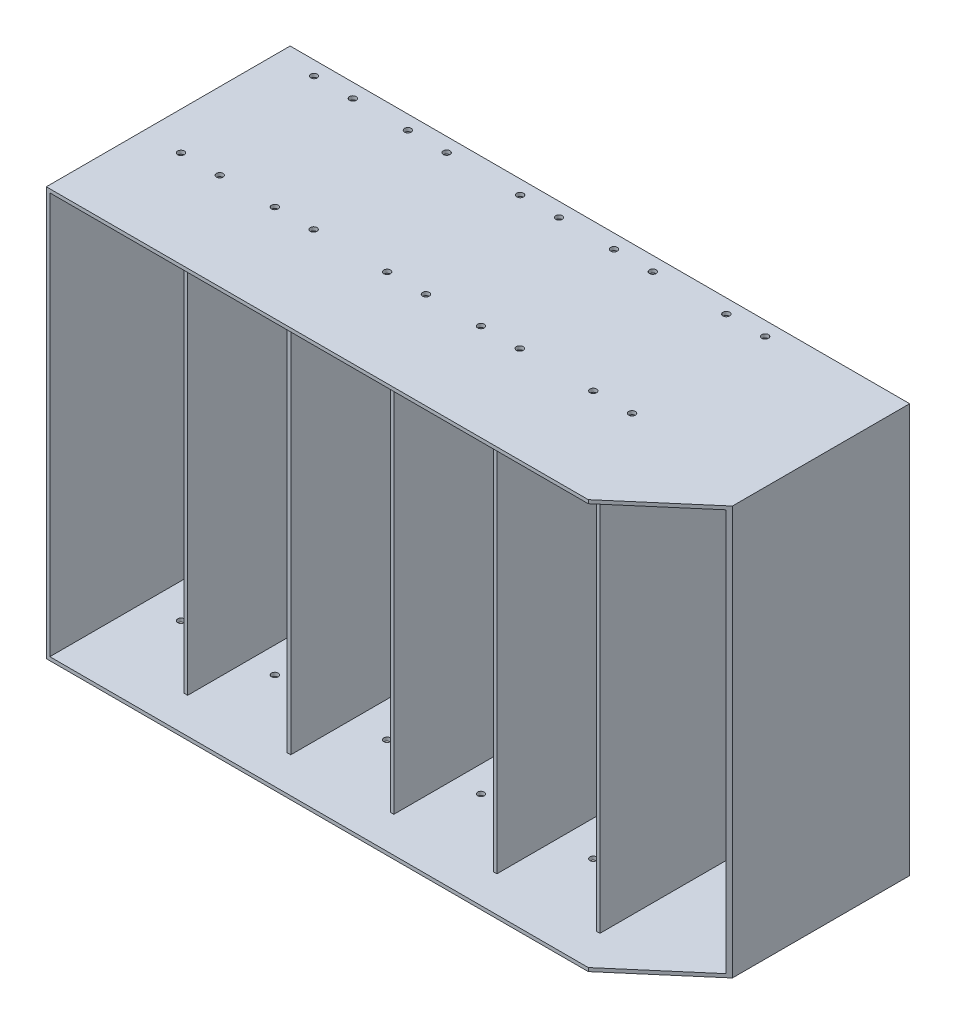
SolidWorks part; units mm, degrees
material "Custom Plastic"
ref_plane "X-Y Datum" through (0, 0, 0) normal (0, 0, 1) x (1, 0, 0)
ref_plane "X-Z Datum" through (0, 0, 0) normal (0, 1, 0) x (1, 0, 0)
ref_plane "Y-Z Datum" through (0, 0, 0) normal (1, 0, 0) x (0, 0, -1)
sketch "Sketch1" plane through (0, 0, 0) normal (0, 0, 1) x (1, 0, 0)
  line L0 (-276.225, 0) -> (276.225, 0) construction
  line L1 (-276.225, 181.1563) -> (276.225, 181.1563)
  line L2 (-276.225, 181.1563) -> (-276.225, -181.1563)
  line L3 (-276.225, -181.1563) -> (276.225, -181.1563)
  line L4 (276.225, 181.1563) -> (276.225, -181.1563)
  line L5 (-276.225, 181.1563) -> (276.225, -181.1563) construction
  line L6 (-276.225, -181.1563) -> (276.225, 181.1563) construction
  line L7 (-273.8438, 178.775) -> (-190.2437, 178.775) construction
  line L8 (-273.8438, 178.775) -> (-273.8438, -178.775) construction
  line L9 (-273.8438, -178.775) -> (-190.2437, -178.775) construction
  line L10 (-190.2437, 178.775) -> (-190.2437, -178.775) construction
  line L11 (-273.8438, 178.775) -> (-190.2437, -178.775) construction
  line L12 (-273.8438, -178.775) -> (-190.2437, 178.775) construction
  line L13 (-187.0687, -181.1563) -> (-187.0687, 181.1563)
  line L14 (-279.4, 184.3313) -> (279.4, 184.3313)
  line L15 (279.4, 184.3313) -> (279.4, -184.3313)
  line L16 (-279.4, -184.3313) -> (279.4, -184.3313)
  line L17 (-279.4, 184.3313) -> (-279.4, -184.3313)
  line L18 (-183.8937, -181.1563) -> (-183.8937, 181.1563)
  line L19 (-187.0687, 0) -> (-183.8937, 0) construction
  line L20 (-180.8797, 178.775) -> (-180.8797, -178.775) construction
  line L21 (-180.8797, 178.775) -> (-97.2797, 178.775) construction
  line L22 (-97.2797, 178.775) -> (-97.2797, -178.775) construction
  line L23 (-180.8797, -178.775) -> (-97.2797, -178.775) construction
  line L24 (-94.1047, -181.1563) -> (-94.1047, 181.1563)
  line L25 (-90.9297, -181.1563) -> (-90.9297, 181.1563)
  line L26 (-87.9157, 178.775) -> (-87.9157, -178.775) construction
  line L27 (-87.9157, 178.775) -> (-4.3157, 178.775) construction
  line L28 (-4.3157, 178.775) -> (-4.3157, -178.775) construction
  line L29 (-87.9157, -178.775) -> (-4.3157, -178.775) construction
  line L30 (-1.1407, -181.1563) -> (-1.1407, 181.1563)
  line L31 (2.0343, -181.1563) -> (2.0343, 181.1563)
  line L32 (5.0483, 178.775) -> (5.0483, -178.775) construction
  line L33 (5.0483, 178.775) -> (88.6483, 178.775) construction
  line L34 (88.6483, 178.775) -> (88.6483, -178.775) construction
  line L35 (5.0483, -178.775) -> (88.6483, -178.775) construction
  line L36 (91.8233, -181.1563) -> (91.8233, 181.1563)
  line L37 (94.9983, -181.1563) -> (94.9983, 181.1563)
  line L38 (98.0123, 178.775) -> (98.0123, -178.775) construction
  line L39 (98.0123, 178.775) -> (181.6123, 178.775) construction
  line L40 (181.6123, 178.775) -> (181.6123, -178.775) construction
  line L41 (98.0123, -178.775) -> (181.6123, -178.775) construction
  line L42 (184.7873, -181.1563) -> (184.7873, 181.1563)
  line L43 (187.9623, -181.1563) -> (187.9623, 181.1563)
  line L44 (-180.8797, -178.775) -> (-97.2797, 178.775) construction
  line L45 (-180.8797, 178.775) -> (-97.2797, -178.775) construction
  line L46 (-87.9157, -178.775) -> (-4.3157, 178.775) construction
  line L47 (-87.9157, 178.775) -> (-4.3157, -178.775) construction
  line L48 (5.0483, -178.775) -> (88.6483, 178.775) construction
  line L49 (5.0483, 178.775) -> (88.6483, -178.775) construction
  line L50 (98.0123, -178.775) -> (181.6123, 178.775) construction
  line L51 (98.0123, 178.775) -> (181.6123, -178.775) construction
  point P0 (0, 0)
  point P6 (-232.0437, 0)
  point P23 (-185.4812, 0)
  point P24 (-139.0797, 0)
  dimension "D1" = 357.55
  dimension "D2" = 83.6
  dimension "D3" = 2.3813
  dimension "D4" = 2.3813
  dimension "D5" = 3.175
  dimension "D8" = 46.5625
  dimension "D10" = 558.8
  dimension "D12" = 92.964
  dimension "D6" = 3.175
  dimension "D7" = 3.175
  dimension "D9" = 5
  dimension "D11" = 5
extrude "Boss-Extrude1" add sketch "Sketch1" along normal blind 3.175 contours L3 L13 L1 L2 | L3 L24 L1 L18 | L3 L18 L1 L13 | L14 L17 L16 L15 L1 L4 L3 L2 | L3 L30 L1 L25 | L3 L25 L1 L24 | L3 L36 L1 L31 | L3 L31 L1 L30 | L3 L42 L1 L37 | L3 L37 L1 L36 | L43 L3 L4 L1 | L3 L43 L1 L42 region at (-231.6469, 0, 0) region at (-185.4812, 0, 0) region at (-138.9992, 0, 0) region at (-92.5172, 0, 0) region at (-46.0352, 0, 0) region at (0.4468, 0, 0) region at (46.9288, 0, 0) region at (93.4108, 0, 0) region at (139.8928, 0, 0) region at (186.3748, 0, 0) region at (232.0936, 0, 0) region at (0, 183.6618, 0)
sketch "Sketch2" plane through (0, 0, 3.175) normal (0, 0, 1) x (1, 0, 0)
  line L0 (-187.0687, -181.1563) -> (-187.0687, 181.1563) construction
  line L1 (-94.1047, -181.1563) -> (-94.1047, 181.1563) construction
  line L2 (-183.8937, -181.1563) -> (-183.8937, 181.1563) construction
  line L3 (91.8233, -181.1563) -> (91.8233, 181.1563) construction
  line L4 (276.225, 181.1563) -> (-276.225, 181.1563)
  line L5 (276.225, -181.1563) -> (276.225, 181.1563)
  line L6 (-276.225, -181.1563) -> (276.225, -181.1563)
  line L7 (-276.225, 181.1563) -> (-276.225, -181.1563)
  line L8 (276.225, 181.1563) -> (-276.225, 181.1563)
  line L9 (276.225, -181.1563) -> (276.225, 181.1563)
  line L10 (-276.225, -181.1563) -> (276.225, -181.1563)
  line L11 (-276.225, 181.1563) -> (-276.225, -181.1563)
  line L12 (-279.4, -184.3313) -> (279.4, -184.3313)
  line L13 (-279.4, 184.3313) -> (-279.4, -184.3313)
  line L14 (279.4, 184.3313) -> (-279.4, 184.3313)
  line L15 (279.4, -184.3313) -> (279.4, 184.3313)
  line L16 (-279.4, -184.3313) -> (279.4, -184.3313)
  line L17 (-279.4, 184.3313) -> (-279.4, -184.3313)
  line L18 (279.4, 184.3313) -> (-279.4, 184.3313)
  line L19 (279.4, -184.3313) -> (279.4, 184.3313)
  line L20 (2.0343, -181.1563) -> (2.0343, 181.1563) construction
  line L21 (-1.1407, -181.1563) -> (-1.1407, 181.1563) construction
  line L22 (-90.9297, -181.1563) -> (-90.9297, 181.1563) construction
  line L23 (187.9623, -181.1563) -> (187.9623, 181.1563) construction
  line L24 (184.7873, -181.1563) -> (184.7873, 181.1563) construction
  line L25 (94.9983, -181.1563) -> (94.9983, 181.1563) construction
  line L26 (-187.0687, -181.1563) -> (-187.0687, 181.1563)
  line L27 (-94.1047, -181.1563) -> (-94.1047, 181.1563)
  line L28 (-183.8937, -181.1563) -> (-183.8937, 181.1563)
  line L29 (91.8233, -181.1563) -> (91.8233, 181.1563)
  line L30 (2.0343, -181.1563) -> (2.0343, 181.1563)
  line L31 (-1.1407, -181.1563) -> (-1.1407, 181.1563)
  line L32 (-90.9297, -181.1563) -> (-90.9297, 181.1563)
  line L33 (187.9623, -181.1563) -> (187.9623, 181.1563)
  line L34 (184.7873, -181.1563) -> (184.7873, 181.1563)
  line L35 (94.9983, -181.1563) -> (94.9983, 181.1563)
  line M9 (279.4, 184.3313) -> (-279.4, 184.3313)
  line M10 (-279.4, 184.3313) -> (-279.4, -184.3313)
  line M11 (-279.4, -184.3313) -> (279.4, -184.3313)
  line M12 (279.4, -184.3313) -> (279.4, 184.3313)
  dimension "D1" = 0
  dimension "D2" = 0
extrude "Boss-Extrude2" add sketch "Sketch2" along normal blind 184.725 contours L11 L8 L9 L10 M12 M9 M10 M11 | L10 L28 L8 L26 | L10 L32 L8 L27 | L31 L10 L30 L8 | L10 L35 L8 L29 | L34 L10 L33 L8 region at (186.3748, 0, 3.175) region at (93.4108, 0, 3.175) region at (0.4468, 0, 3.175) region at (-92.5172, 0, 3.175) region at (-185.4812, 0, 3.175) region at (-278.7305, 0, 3.175)
sketch "Sketch3" plane through (0, 0, 187.9) normal (0, 0, 1) x (1, 0, 0)
  line L0 (-187.0687, -181.1563) -> (-187.0687, 181.1563) construction
  line L1 (-94.1047, -181.1563) -> (-94.1047, 181.1563) construction
  line L2 (-183.8937, -181.1563) -> (-183.8937, 181.1563) construction
  line L3 (91.8233, -181.1563) -> (91.8233, 181.1563) construction
  line L4 (276.225, 181.1563) -> (-276.225, 181.1563)
  line L5 (276.225, -181.1563) -> (276.225, 181.1563)
  line L6 (-276.225, -181.1563) -> (276.225, -181.1563)
  line L7 (-276.225, 181.1563) -> (-276.225, -181.1563)
  line L8 (276.225, 181.1563) -> (-276.225, 181.1563)
  line L9 (276.225, -181.1563) -> (276.225, 181.1563)
  line L10 (-276.225, -181.1563) -> (276.225, -181.1563)
  line L11 (-276.225, 181.1563) -> (-276.225, -181.1563)
  line L12 (-279.4, -184.3313) -> (279.4, -184.3313)
  line L13 (-279.4, 184.3313) -> (-279.4, -184.3313)
  line L14 (279.4, 184.3313) -> (-279.4, 184.3313)
  line L15 (279.4, -184.3313) -> (279.4, 184.3313)
  line L16 (-279.4, -184.3313) -> (279.4, -184.3313)
  line L17 (-279.4, 184.3313) -> (-279.4, -184.3313)
  line L18 (279.4, 184.3313) -> (-279.4, 184.3313)
  line L19 (279.4, -184.3313) -> (279.4, 184.3313)
  line L20 (2.0343, -181.1563) -> (2.0343, 181.1563) construction
  line L21 (-1.1407, -181.1563) -> (-1.1407, 181.1563) construction
  line L22 (-90.9297, -181.1563) -> (-90.9297, 181.1563) construction
  line L23 (187.9623, -181.1563) -> (187.9623, 181.1563) construction
  line L24 (184.7873, -181.1563) -> (184.7873, 181.1563) construction
  line L25 (94.9983, -181.1563) -> (94.9983, 181.1563) construction
  line L26 (-187.0687, -181.1563) -> (-187.0687, 181.1563)
  line L27 (-94.1047, -181.1563) -> (-94.1047, 181.1563)
  line L28 (-183.8937, -181.1563) -> (-183.8937, 181.1563)
  line L29 (91.8233, -181.1563) -> (91.8233, 181.1563)
  line L30 (2.0343, -181.1563) -> (2.0343, 181.1563)
  line L31 (-1.1407, -181.1563) -> (-1.1407, 181.1563)
  line L32 (-90.9297, -181.1563) -> (-90.9297, 181.1563)
  line L33 (187.9623, -181.1563) -> (187.9623, 181.1563)
  line L34 (184.7873, -181.1563) -> (184.7873, 181.1563)
  line L35 (94.9983, -181.1563) -> (94.9983, 181.1563)
  line M9 (94.9983, 181.1563) -> (184.7873, 181.1563)
  line M11 (184.7873, -181.1563) -> (94.9983, -181.1563)
  line M13 (2.0343, 181.1563) -> (91.8233, 181.1563)
  line M15 (91.8233, -181.1563) -> (2.0343, -181.1563)
  line M17 (-90.9297, 181.1563) -> (-1.1407, 181.1563)
  line M19 (-1.1407, -181.1563) -> (-90.9297, -181.1563)
  line M21 (-183.8937, 181.1563) -> (-94.1047, 181.1563)
  line M23 (-94.1047, -181.1563) -> (-183.8937, -181.1563)
  line M25 (-276.225, 181.1563) -> (-187.0687, 181.1563)
  line M27 (-187.0687, -181.1563) -> (-276.225, -181.1563)
  line M28 (-276.225, -181.1563) -> (-276.225, 181.1563)
  line M30 (187.9623, 181.1563) -> (276.225, 181.1563)
  line M31 (276.225, 181.1563) -> (276.225, -181.1563)
  line M32 (276.225, -181.1563) -> (187.9623, -181.1563)
  line M33 (279.4, -184.3313) -> (279.4, 184.3313)
  line M34 (279.4, 184.3313) -> (-279.4, 184.3313)
  line M35 (-279.4, 184.3313) -> (-279.4, -184.3313)
  line M36 (-279.4, -184.3313) -> (279.4, -184.3313)
  dimension "D1" = 0
  dimension "D2" = 0
extrude "Boss-Extrude3" add sketch "Sketch3" along normal blind 32 contours L10 L8 M36 M33 M34 M35 M27 M28 M25 M21 M17 M13 M9 M30 M31 M32 M11 M15 M19 M23 region at (-278.7305, 0, 187.9)
sketch "Sketch4" plane through (0, -184.3313, 0) normal (0, -1, 0) x (1, 0, 0)
  line L0 (209.4, 219.9) -> (279.4, 159.9)
  line L1 (-279.4, 219.9) -> (279.4, 219.9) construction
  line L2 (279.4, 219.9) -> (279.4, 0) construction
  line M3 (279.4, 0) -> (279.4, 219.9)
  line M4 (279.4, 219.9) -> (-279.4, 219.9)
  dimension "D1" = 60
  dimension "D2" = 70
extrude "Cut-Extrude1" cut sketch "Sketch4" against normal through all contours L0 M4 M3 region at (256.0667, -184.3313, 199.9)
sketch "Sketch5" plane through (0, -184.3313, 0) normal (0, -1, 0) x (1, 0, 0)
  circle A0 centre (-210.1469, 12.7) radius 3 construction
  circle A1 centre (-245.1469, 12.7) radius 3 construction
  circle A2 centre (-210.1469, 132.7) radius 3 construction
  circle A3 centre (-245.1469, 132.7) radius 3 construction
  circle A4 centre (-210.1469, 12.7) radius 3
  circle A5 centre (-245.1469, 12.7) radius 3
  circle A6 centre (-210.1469, 132.7) radius 3
  circle A7 centre (-245.1469, 132.7) radius 3
extrude "Cut-Extrude2" cut sketch "Sketch5" against normal through all
pattern_linear "LPattern1" count 3 spacing 185.928 along (1, 0, 0) of "Cut-Extrude2"
sketch "Sketch6" plane through (0, -184.3313, 0) normal (0, -1, 0) x (1, 0, 0)
  circle A0 centre (-125.4993, 132.7) radius 3 construction
  circle A1 centre (-160.4993, 132.7) radius 3 construction
  circle A2 centre (-125.4993, 12.7) radius 3 construction
  circle A3 centre (-160.4993, 12.7) radius 3 construction
  circle A4 centre (-125.4993, 132.7) radius 3
  circle A5 centre (-160.4993, 132.7) radius 3
  circle A6 centre (-125.4993, 12.7) radius 3
  circle A7 centre (-160.4993, 12.7) radius 3
extrude "Cut-Extrude3" cut sketch "Sketch6" against normal through all
pattern_linear "LPattern2" count 2 spacing 185.928 along (1, 0, 0) of "Cut-Extrude3"
